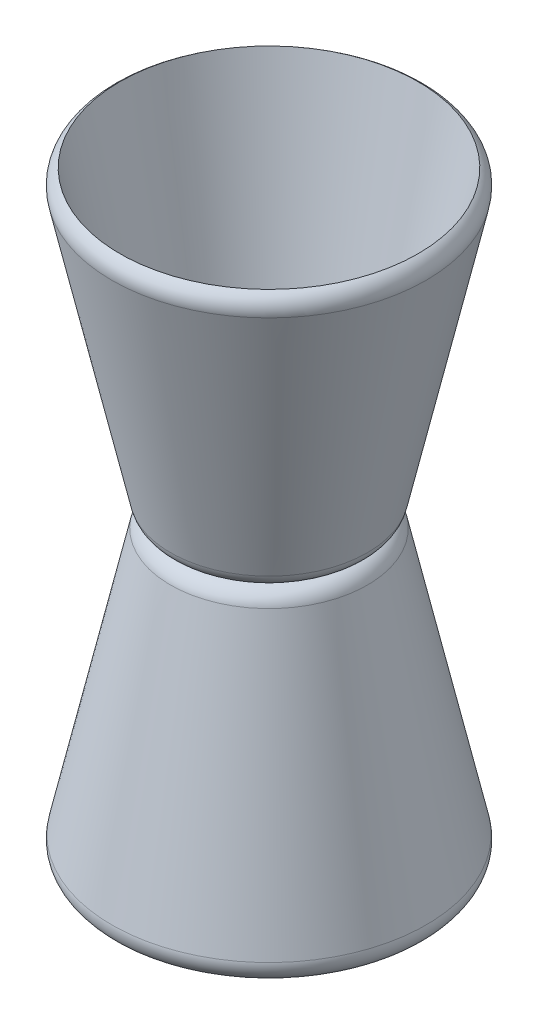
SolidWorks part; units mm, degrees
ref_plane "Front Plane" through (0, 0, 0) normal (0, 0, 1) x (1, 0, 0)
ref_plane "Top Plane" through (0, 0, 0) normal (0, 1, 0) x (1, 0, 0)
ref_plane "Right Plane" through (0, 0, 0) normal (1, 0, 0) x (0, 0, -1)
sketch "Sketch1" plane through (0, 0, 0) normal (0, 0, 1) x (1, 0, 0)
  line L0 (0, -330.8417) -> (0, -380.8417)
  line L1 (0, -380.8417) -> (160, -380.8417)
  line L2 (160, -380.8417) -> (270.4824, 119.1583)
  line L3 (270.4824, 119.1583) -> (250, 119.1583)
  line L8 (0, -330.8417) -> (150.5658, -330.8417)
  line L9 (150.5658, -330.8417) -> (250, 119.1583)
  point P0 (0, 0)
  dimension "D1" = 20
  dimension "D2" = 500
  dimension "D3" = 160
  dimension "D4" = 250
  dimension "D5" = 50
revolve "Revolve1" add sketch "Sketch1" angle 360 about L0
fillet "Fillet1" radius 30 2 edges at (-160, -380.8417, 0) (-270.4824, 119.1583, 0)
mirror "Mirror1" about plane through (0, -380.8417, 0) normal (0, 1, 0) of "Revolve1", "Fillet1"
